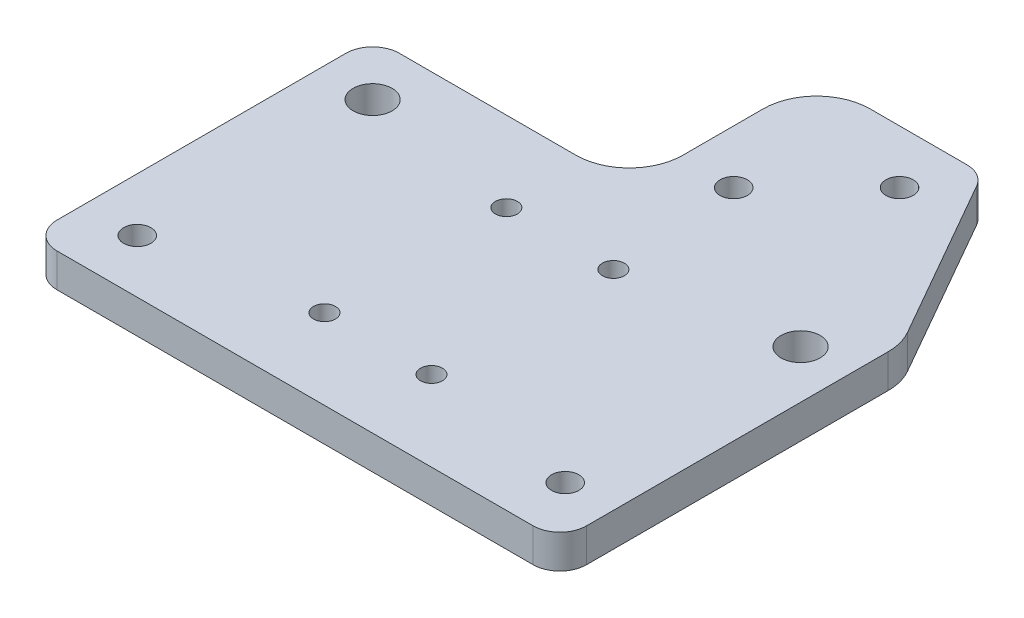
SolidWorks part; units mm, degrees
ref_plane "Front Plane" through (0, 0, 0) normal (0, 0, 1) x (1, 0, 0)
ref_plane "Top Plane" through (0, 0, 0) normal (0, 1, 0) x (1, 0, 0)
ref_plane "Right Plane" through (0, 0, 0) normal (1, 0, 0) x (0, 0, -1)
sketch "Sketch1" plane through (0, 0, 0) normal (0, 1, 0) x (1, 0, 0)
  line L0 (0, 64) -> (48, 64)
  line L1 (0, 0) -> (99, 0)
  line L2 (0, 0) -> (0, 64)
  line L3 (48, 99) -> (79, 99)
  line L4 (99, 0) -> (99, 64)
  line L5 (48, 64) -> (48, 99)
  line L6 (99, 64) -> (79, 99)
  line L7 (90, 54) -> (10, 54) construction
  line L8 (10, 54) -> (10, 10) construction
  line L9 (10, 10) -> (90, 10) construction
  line L10 (90, 10) -> (90, 54) construction
  line L11 (40, 15) -> (40, 49) construction
  line L12 (40, 49) -> (60, 49) construction
  line L13 (60, 49) -> (60, 15) construction
  line L14 (60, 15) -> (40, 15) construction
  circle A0 centre (10, 10) radius 2.55
  circle A1 centre (90, 10) radius 2.55
  circle A2 centre (90, 54) radius 3.65
  circle A3 centre (10, 54) radius 3.65
  circle A4 centre (40, 49) radius 2.05
  circle A5 centre (60, 49) radius 2.05
  circle A6 centre (60, 15) radius 2.05
  circle A7 centre (40, 15) radius 2.05
  circle A8 centre (73.5, 89) radius 2.55
  circle A9 centre (58, 73.5) radius 2.55
  dimension "D8" = 7.3
  dimension "D9" = 7.3
  dimension "D12" = 5.1
  dimension "D13" = 5.1
  dimension "D18" = 4.1
  dimension "D19" = 4.1
  dimension "D20" = 4.1
  dimension "D21" = 4.1
  dimension "D23" = 5.1
  dimension "D25" = 5.1
  dimension "D28" = 35
  dimension "D1" = 64
  dimension "D3" = 48
  dimension "D4" = 35
  dimension "D5" = 20
  dimension "D6" = 10
  dimension "D7" = 80
  dimension "D10" = 10
  dimension "D11" = 10
  dimension "D14" = 15
  dimension "D15" = 15
  dimension "D16" = 40
  dimension "D17" = 20
  dimension "D22" = 89
  dimension "D24" = 73.5
  dimension "D26" = 58
  dimension "D27" = 73.5
  dimension "D29" = 150.255
extrude "Boss-Extrude2" add sketch "Sketch1" along normal blind 6.3 contours L2 L0 L5 L3 L6 L4 L1
extrude "Cut-Extrude3" cut sketch "Sketch1<7>" along normal through all contours A8
sketch "Sketch1<7>" plane through (0, 0, 0) normal (0, 1, 0) x (1, 0, 0) same geometry as "Sketch1"
extrude "Cut-Extrude4" cut sketch "Sketch1<8>" along normal through all contours A2
sketch "Sketch1<8>" plane through (0, 0, 0) normal (0, 1, 0) x (1, 0, 0) same geometry as "Sketch1"
extrude "Cut-Extrude5" cut sketch "Sketch1<9>" along normal through all contours A9
sketch "Sketch1<9>" plane through (0, 0, 0) normal (0, 1, 0) x (1, 0, 0) same geometry as "Sketch1"
extrude "Cut-Extrude6" cut sketch "Sketch1<10>" along normal through all contours A3
sketch "Sketch1<10>" plane through (0, 0, 0) normal (0, 1, 0) x (1, 0, 0) same geometry as "Sketch1"
extrude "Cut-Extrude8" cut sketch "Sketch1<11>" along normal through all contours A5
sketch "Sketch1<11>" plane through (0, 0, 0) normal (0, 1, 0) x (1, 0, 0) same geometry as "Sketch1"
extrude "Cut-Extrude10" cut sketch "Sketch1<12>" along normal through all contours A4
sketch "Sketch1<12>" plane through (0, 0, 0) normal (0, 1, 0) x (1, 0, 0) same geometry as "Sketch1"
extrude "Cut-Extrude11" cut sketch "Sketch1<13>" along normal through all contours A1
sketch "Sketch1<13>" plane through (0, 0, 0) normal (0, 1, 0) x (1, 0, 0) same geometry as "Sketch1"
extrude "Cut-Extrude12" cut sketch "Sketch1<14>" along normal through all contours A6
sketch "Sketch1<14>" plane through (0, 0, 0) normal (0, 1, 0) x (1, 0, 0) same geometry as "Sketch1"
extrude "Cut-Extrude13" cut sketch "Sketch1<15>" along normal through all contours A7
sketch "Sketch1<15>" plane through (0, 0, 0) normal (0, 1, 0) x (1, 0, 0) same geometry as "Sketch1"
extrude "Cut-Extrude14" cut sketch "Sketch1<16>" along normal through all contours A0
sketch "Sketch1<16>" plane through (0, 0, 0) normal (0, 1, 0) x (1, 0, 0) same geometry as "Sketch1"
fillet "Fillet1" radius 5 3 edges at (0, 3.15, -64) (0, 3.15, 0) (99, 3.15, 0)
fillet "Fillet2" radius 5 1 edges at (79, 3.15, -99)
fillet "Fillet3" radius 10 1 edges at (48, 3.15, -99)
fillet "Fillet4" radius 10 1 edges at (99, 3.15, -64)
fillet "Fillet5" radius 10 1 edges at (48, 3.15, -64)
